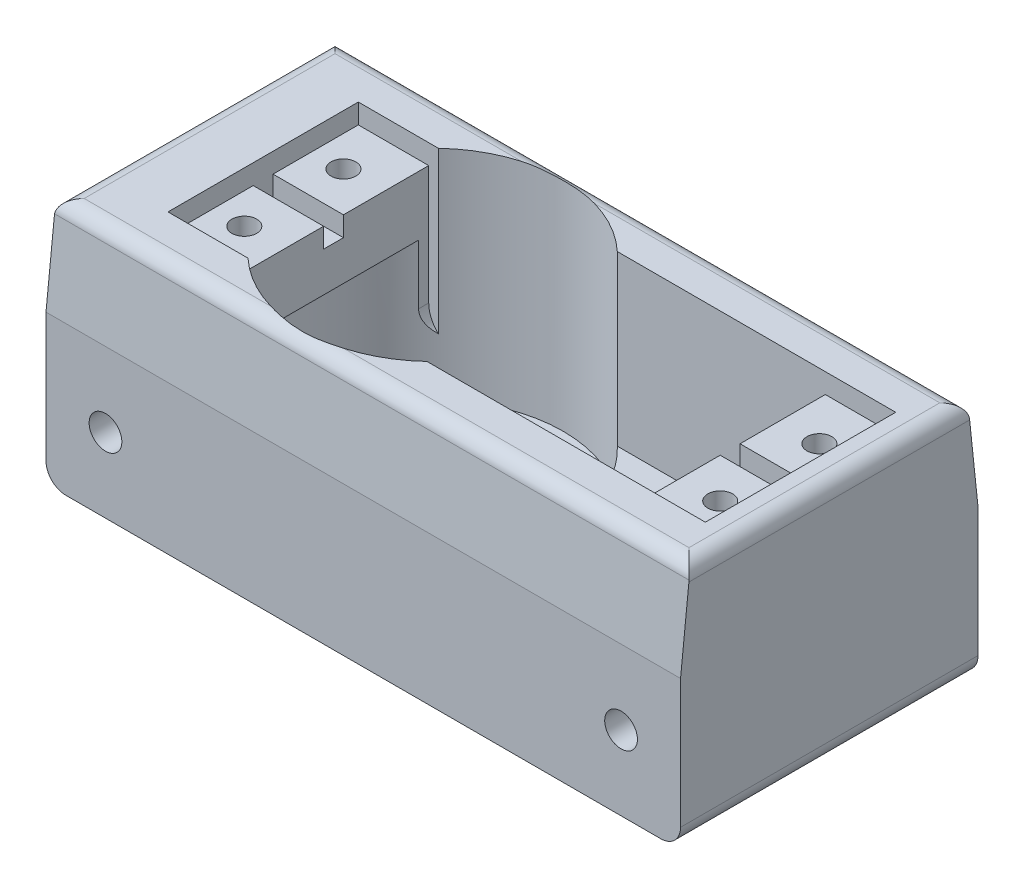
SolidWorks part; units mm, degrees
ref_plane "Спереди" through (0, 0, 0) normal (0, 0, 1) x (1, 0, 0)
ref_plane "Сверху" through (0, 0, 0) normal (0, 1, 0) x (1, 0, 0)
ref_plane "Справа" through (0, 0, 0) normal (1, 0, 0) x (0, 0, -1)
sketch "Эскиз1" plane through (0, 0, 0) normal (0, 1, 0) x (1, 0, 0)
  line L0 (0, 15) -> (0, -15) construction
  line L1 (-24, 15) -> (40, 15)
  line L2 (-24, 15) -> (-24, -15)
  line L3 (-24, -15) -> (40, -15)
  line L4 (40, 15) -> (40, -15)
  line L6 (-24, 0) -> (40, 0) construction
  point P6 (0, 0)
  dimension "D1" = 30
  dimension "D2" = 24
  dimension "D3" = 40
extrude "тело для подшипников" add sketch "Эскиз1" along normal blind 7.5
sketch "Эскиз2" plane through (0, 7.5, 0) normal (0, 1, 0) x (1, 0, 0)
  circle A0 centre (0, 0) radius 13.175
  dimension "D1" = 26.35
extrude "подшипник верхний" cut sketch "Эскиз2" against normal blind 5
sketch "Эскиз4" plane through (0, 2.5, 0) normal (0, 1, 0) x (1, 0, 0)
  circle A0 centre (0, 0) radius 11.5
  dimension "D1" = 23
extrude "отверстие под ось" cut sketch "Эскиз4" against normal through all
sketch "Эскиз8" plane through (0, 7.5, 0) normal (0, 1, 0) x (1, 0, 0)
  line L0 (-24, 0) -> (40, 0) construction
  line L1 (-24, 15) -> (40, 15)
  line L2 (-24, 15) -> (-24, -15)
  line L3 (-24, -15) -> (40, -15)
  line L4 (40, 15) -> (40, -15)
  line L5 (-24, 15) -> (-24, -15) construction
  line L6 (0, 15) -> (0, -15) construction
  circle A0 centre (0, 0) radius 13.175
  circle A1 centre (0, 0) radius 13.175 construction
  dimension "D2" = 40
extrude "основание под сервой" add sketch "Эскиз8" along normal blind 3
sketch "Эскиз9" plane through (0, 10.5, 0) normal (0, 1, 0) x (1, 0, 0)
  line L0 (40, 15) -> (-24, 15) construction
  line L1 (-20, 15) -> (-10, 15)
  line L2 (-20, 15) -> (-20, -15)
  line L3 (-20, -15) -> (-10, -15)
  line L4 (-10, 15) -> (-10, 8.5779)
  line L5 (-24, -15) -> (40, -15) construction
  line L6 (0, 15) -> (0, -15) construction
  line L7 (40, 15) -> (30, 15)
  line L8 (40, 15) -> (40, -15)
  line L9 (40, -15) -> (30, -15)
  line L10 (30, 15) -> (30, -15)
  line L11 (-10, -8.5779) -> (-10, -15)
  arc A0 (-10, 8.5779) -> (-10, -8.5779) centre (0, 0) ccw
  circle A1 centre (0, 0) radius 13.175 construction
  dimension "D1" = 20
  dimension "D2" = 40
  dimension "D3" = 10
  dimension "D4" = 10
extrude "выступы к серве" add sketch "Эскиз9" along normal blind 12
sketch "Эскиз10" plane through (0, 22.5, 0) normal (0, 1, 0) x (1, 0, 0)
  line L0 (-20, 0) -> (40, 0) construction
  line L1 (-20, 15) -> (-20, -15) construction
  line L2 (40, -15) -> (40, 15) construction
  line L3 (-14, 5) -> (-14, -5) construction
  line L5 (34, 5) -> (34, -5) construction
  circle A0 centre (-14, 5) radius 1.25
  circle A1 centre (-14, -5) radius 1.25
  circle A2 centre (34, -5) radius 1.25
  circle A3 centre (34, 5) radius 1.25
  point P14 (34, 0)
  point P15 (-14, 0)
  dimension "D1" = 2.5
  dimension "D2" = 10
  dimension "D3" = 14
  dimension "D4" = 34
extrude "крепление сервы" cut sketch "Эскиз10" against normal blind 11
sketch "Эскиз11" plane through (0, 0, 15) normal (0, 0, 1) x (1, 0, 0)
  line L0 (-24, 7.5) -> (40, 7.5) construction
  line L2 (40, 22.5) -> (40, 0) construction
  line L4 (0, 10.5) -> (0, 0) construction
  line L5 (8, 0) -> (8, 10.5) construction
  line L6 (-10, 10.5) -> (30, 10.5) construction
  line L8 (-24, 0) -> (40, 0) construction
  circle A0 centre (-18, 7.5) radius 1.65
  circle A3 centre (34, 7.5) radius 1.65
  dimension "D1" = 3.3
  dimension "D2" = 52
  dimension "D3" = 7.5
extrude "Отверстия для шурупов" cut sketch "Эскиз11" against normal through all
mirror "Отверстия для шурупов с другой стороны" [suppressed] about plane through (0, 0, 0) normal (0, 0, 1)
sketch "Эскиз12" plane through (0, 22.5, 0) normal (0, 1, 0) x (1, 0, 0)
  line L0 (-10, -15) -> (-10, -8.5779) construction
  line L1 (-10, 8.5779) -> (-10, 15) construction
  line L2 (-20, 15) -> (-10, 15)
  line L3 (-20, 15) -> (-20, 9.6)
  line L4 (-20, 9.6) -> (-10, 9.6)
  line L5 (-20, -15) -> (-10, -15)
  line L6 (-10, 15) -> (-10, 9.6)
  line L7 (-20, -15) -> (-20, -9.6)
  line L8 (-20, -9.6) -> (-10, -9.6)
  line L9 (-10, -15) -> (-10, -9.6)
  line L10 (30, 15) -> (30, -15) construction
  line L11 (40, -15) -> (30, -15)
  line L12 (40, -15) -> (40, -9.6)
  line L13 (40, -9.6) -> (30, -9.6)
  line L14 (30, -15) -> (30, -9.6)
  line L15 (40, 15) -> (30, 15) construction
  line L16 (40, 15) -> (30, 15)
  line L17 (40, 15) -> (40, 9.6)
  line L18 (40, 9.6) -> (30, 9.6)
  line L19 (30, 15) -> (30, 9.6)
  line L20 (40, -15) -> (40, 15) construction
  dimension "D1" = 5.4
extrude "бортики к серве" add sketch "Эскиз12" along normal blind 2
sketch "Эскиз14" plane through (0, 10.5, 0) normal (0, 1, 0) x (1, 0, 0)
  line L0 (-10, 15) -> (-10, 8.5779)
  line L1 (-10, 15) -> (30, 15)
  line L2 (30, 15) -> (30, -15)
  line L3 (30, -15) -> (-10, -15)
  line L4 (-10, -15) -> (-10, -8.5779)
  arc A0 (-10, -8.5779) -> (-10, 8.5779) centre (0, 0) ccw
  arc A1 (-10, -8.5779) -> (-10, 8.5779) centre (0, 0) ccw construction
extrude "углубление впресовать подшипник" cut sketch "Эскиз14" against normal blind 3
sketch "Эскиз15" plane through (0, 22.5, 0) normal (0, 1, 0) x (1, 0, 0)
  line L1 (-20, 9.6) -> (-10, 9.6)
  line L2 (-20, 9.6) -> (-20, -9.6)
  line L3 (-20, -9.6) -> (-10, -9.6)
  line L4 (-10, 9.6) -> (-10, -9.6)
  circle A0 centre (-14, 5) radius 1.25
  circle A1 centre (-14, -5) radius 1.25
  circle A2 centre (-14, 5) radius 1.25 construction
  circle A3 centre (-14, -5) radius 1.25 construction
extrude "наплыв для саморезов" add sketch "Эскиз15" against normal blind 9
chamfer "Фаска5" distance 3 angle 45 1 edges at (-10, 13.5, 0)
sketch "Эскиз17" plane through (0, 22.5, 0) normal (0, 1, 0) x (1, 0, 0)
  line L0 (-10, -9.6) -> (-20, -9.6) construction
  line L1 (-20, 9.6) -> (-17.1, 9.6)
  line L2 (-20, 9.6) -> (-20, -9.6)
  line L3 (-20, -9.6) -> (-17.1, -9.6)
  line L4 (-17.1, 9.6) -> (-17.1, -9.6)
  line L5 (40, -9.6) -> (30, -9.6) construction
  line L6 (40, 9.6) -> (37.1, 9.6)
  line L7 (40, 9.6) -> (40, -9.6)
  line L8 (40, -9.6) -> (37.1, -9.6)
  line L9 (37.1, 9.6) -> (37.1, -9.6)
  line L10 (-20, 9.6) -> (-10, 9.6) construction
  line L11 (-20, 15) -> (-20, -15) construction
  line L12 (-20, 9.6) -> (-20, -9.6) construction
  dimension "D1" = 2.9
  dimension "D2" = 2.9
extrude "бортики к серве спереди" add sketch "Эскиз17" along normal up to surface (2 mm away) up to face at (-15, 24.5, -12.3)
sketch "Эскиз16" plane through (0, 22.5, 0) normal (0, 1, 0) x (1, 0, 0)
  line L0 (-17.1, 0) -> (37.1, 0) construction
  line L3 (-10, -9.6) -> (-10, 9.6) construction
  line L4 (-10, 1) -> (-17.1, 1)
  line L5 (-10, 1) -> (-10, -1)
  line L6 (-10, -1) -> (-17.1, -1)
  line L7 (-17.1, 1) -> (-17.1, -1)
  line L8 (30, 9.6) -> (30, -9.6) construction
  line L9 (30, -1) -> (37.1, -1)
  line L10 (30, -1) -> (30, 1)
  line L11 (30, 1) -> (37.1, 1)
  line L12 (37.1, -1) -> (37.1, 1)
  line L13 (-17.1, -9.6) -> (-17.1, 9.6) construction
  line L14 (-17.1, -9.6) -> (-17.1, 9.6) construction
  line L15 (37.1, 9.6) -> (37.1, -9.6) construction
  point P12 (-10, 0)
  point P19 (30, 0)
  dimension "D1" = 2
extrude "пазы под ребра жесткости сервы" cut sketch "Эскиз16" against normal blind 2
sketch "Эскиз18" plane through (0, 10.5, 0) normal (0, 1, 0) x (1, 0, 0)
  line L0 (-20, -15) -> (-10, -15) construction
  line L1 (-24, 15) -> (-20, 15)
  line L2 (-24, 15) -> (-24, -15)
  line L3 (-24, -15) -> (-20, -15)
  line L4 (-20, 15) -> (-20, -15)
  line L5 (-20, 15) -> (-20, -15) construction
extrude "площадка под светодиод" add sketch "Эскиз18" along normal up to surface (14 mm away) up to face at (-14.275, 24.5, 0)
sketch "Эскиз19" plane through (0, 7.5, 0) normal (0, 1, 0) x (1, 0, 0)
  line L0 (30, -15) -> (30, 15) construction
  line L1 (-10, 15) -> (30, 15)
  line L2 (-10, 15) -> (-10, 13.175)
  line L3 (-10, 13.175) -> (30, 13.175)
  line L4 (30, 15) -> (30, 13.175)
  line L5 (30, 15) -> (30, 9.6) construction
  line L6 (0, 0) -> (30, 0) construction
  line L7 (30, 1) -> (30, -1) construction
  line L8 (-10, -13.175) -> (30, -13.175)
  line L9 (30, -15) -> (30, -13.175)
  line L10 (-10, -15) -> (30, -15)
  line L11 (-10, -15) -> (-10, -13.175)
  circle A0 centre (0, 0) radius 13.175 construction
extrude "Бордюры-ребра жесткости" [suppressed] add sketch "Эскиз19" along normal up to surface (17 mm away) up to face at (-15.275, 24.5, 0)
fillet "Скругление4" radius 3 3 edges at (30, 7.5, 0) (-10, 7.5, -11.789) (-10, 7.5, 11.789)
fillet "Скругление5" radius 2 2 edges at (-24, 0, 0) (40, 0, 0)
chamfer "Фаска6" [suppressed] distance 0.5 angle 45
chamfer "Фаска7" distance 9.5 distance2 1 2 edges at (35, 24.5, 15) (-17, 24.5, 15) first distance on face at (9, 11.3274, 15)
chamfer "Фаска8" distance 9.5 distance2 1 2 edges at (-17, 24.5, -15) (35, 24.5, -15) first distance on face at (9, 11.3274, -15)
fillet "Скругление6" radius 1.5 6 edges at (35, 24.5, 14) (40, 24.5, 0) (35, 24.5, -14) (-17, 24.5, 14) (-24, 24.5, 0) (-17, 24.5, -14)
sketch "Эскиз20" plane through (-10, 0, 0) normal (1, 0, 0) x (0, 0, -1)
  line L0 (15, 15) -> (14.1579, 23) construction
  line L1 (9.6, 24.5) -> (12.6496, 24.5)
  line L2 (9.6, 24.5) -> (9.6, 7.5)
  line L3 (9.6, 7.5) -> (15, 7.5)
  line L4 (14.1414, 23.157) -> (15, 15)
  line L5 (15, 15) -> (15, 7.5)
  line L6 (15, 15) -> (15, 2) construction
  arc A0 (12.6496, 24.5) -> (14.1414, 23.157) centre (12.6496, 23) cw
  arc A1 (14.1414, 23.157) -> (12.6496, 24.5) centre (12.6496, 23) ccw construction
  point P1 (0, 0)
extrude "Ребро_жесткости_доп" add sketch "Эскиз20" along normal up to next
sketch "Эскиз22" plane through (0, 7.5, 0) normal (0, -1, 0) x (1, 0, 0)
  line L0 (-10, -8.5779) -> (-10, 8.5779)
  line L3 (-10, 8.5779) -> (-10, -8.5779) construction
  arc A0 (-10, -8.5779) -> (-10, 8.5779) centre (0, 0) ccw
  circle A3 centre (0, 0) radius 13.175 construction
  point P1 (-10.2762, -7.5153)
  point P8 (-10, -8.5779)
  point P10 (-10.1161, 8.4407)
extrude "Под подшипник в боковых стенках" cut sketch "Эскиз22" against normal through all
mirror "Зеркальное отражение1" about plane through (0, 0, 0) normal (0, 0, 1) of "Ребро_жесткости_доп", "Под подшипник в боковых стенках"
